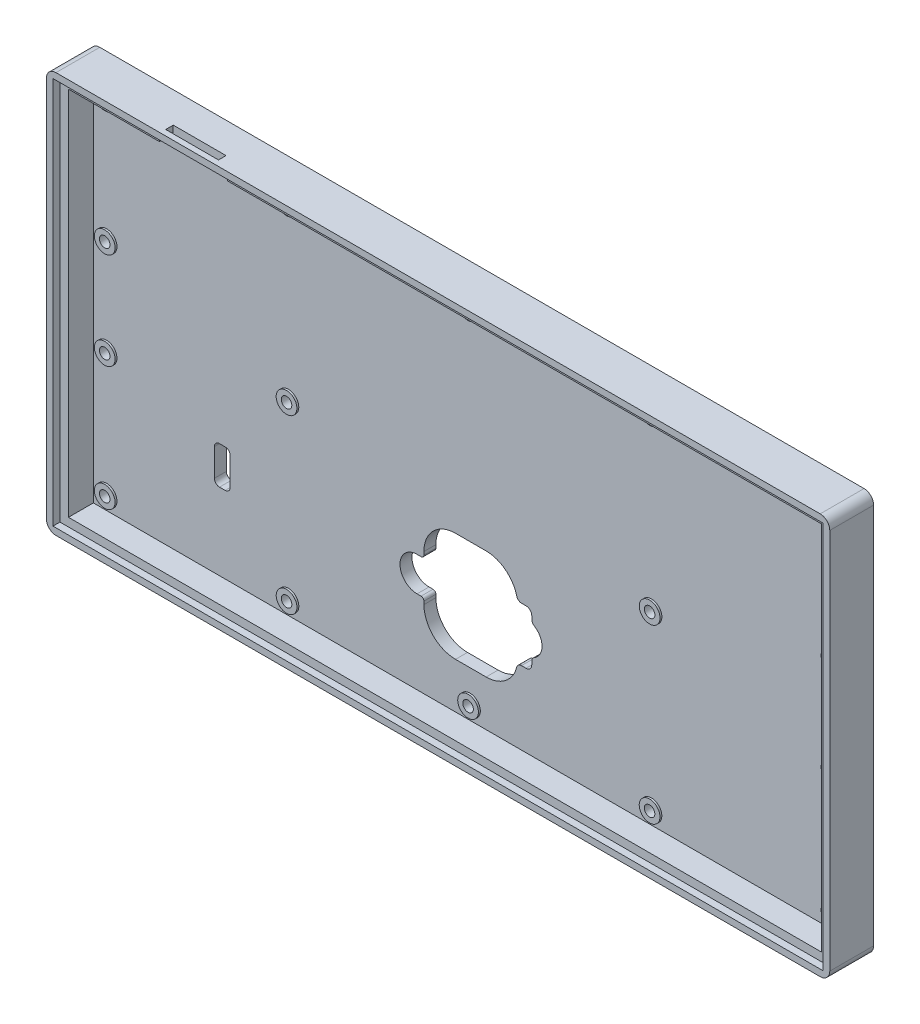
SolidWorks part; units mm, degrees
ref_plane "Front Plane" through (0, 0, 0) normal (0, 0, 1) x (1, 0, 0)
ref_plane "Top Plane" through (0, 0, 0) normal (0, 1, 0) x (1, 0, 0)
ref_plane "Right Plane" through (0, 0, 0) normal (1, 0, 0) x (0, 0, -1)
sketch "PCB" plane through (0, 0, 0) normal (0, 0, 1) x (1, 0, 0)
  line L0 (96.2635, 45.5524) -> (101.8921, 45.5524) construction
  line L1 (-101.8921, 51.181) -> (101.8921, 51.181) construction
  line L2 (-101.8921, 51.181) -> (-101.8921, -51.181) construction
  line L3 (-101.8921, -51.181) -> (101.8921, -51.181) construction
  line L4 (101.8921, 51.181) -> (101.8921, -51.181) construction
  line L5 (-101.8921, 51.181) -> (101.8921, -51.181) construction
  line L6 (-101.8921, -51.181) -> (101.8921, 51.181) construction
  line L7 (96.2635, 45.5524) -> (96.2635, 51.181) construction
  line L8 (-96.2635, 45.5524) -> (-101.8921, 45.5524) construction
  line L9 (-96.2635, -45.5524) -> (-96.2635, -51.181) construction
  line L10 (-92.8243, 0) -> (-92.8243, 25.6794) construction
  line L11 (-98.8568, 31.7119) -> (-86.7918, 31.7119)
  line L12 (-98.8568, 31.7119) -> (-98.8568, 19.6469)
  line L13 (-98.8568, 19.6469) -> (-86.7918, 19.6469)
  line L14 (-86.7918, 31.7119) -> (-86.7918, 19.6469)
  line L15 (-98.8568, 31.7119) -> (-86.7918, 19.6469) construction
  line L16 (-98.8568, 19.6469) -> (-86.7918, 31.7119) construction
  line L17 (-98.8568, 6.0325) -> (-86.7918, 6.0325)
  line L18 (-98.8568, 6.0325) -> (-98.8568, -6.0325)
  line L19 (-98.8568, -6.0325) -> (-86.7918, -6.0325)
  line L20 (-86.7918, 6.0325) -> (-86.7918, -6.0325)
  line L21 (-98.8568, 6.0325) -> (-86.7918, -6.0325) construction
  line L22 (-98.8568, -6.0325) -> (-86.7918, 6.0325) construction
  line L23 (-98.8568, -19.6469) -> (-86.7918, -19.6469)
  line L24 (-98.8568, -19.6469) -> (-98.8568, -31.7119)
  line L25 (-98.8568, -31.7119) -> (-86.7918, -31.7119)
  line L26 (-86.7918, -19.6469) -> (-86.7918, -31.7119)
  line L27 (-98.8568, -19.6469) -> (-86.7918, -31.7119) construction
  line L28 (-98.8568, -31.7119) -> (-86.7918, -19.6469) construction
  line L29 (86.7918, 31.7119) -> (98.8568, 31.7119)
  line L30 (86.7918, 31.7119) -> (86.7918, 19.6469)
  line L31 (86.7918, 19.6469) -> (98.8568, 19.6469)
  line L32 (98.8568, 31.7119) -> (98.8568, 19.6469)
  line L33 (86.7918, 31.7119) -> (98.8568, 19.6469) construction
  line L34 (86.7918, 19.6469) -> (98.8568, 31.7119) construction
  line L35 (86.7918, 6.0325) -> (98.8568, 6.0325)
  line L36 (86.7918, 6.0325) -> (86.7918, -6.0325)
  line L37 (86.7918, -6.0325) -> (98.8568, -6.0325)
  line L38 (98.8568, 6.0325) -> (98.8568, -6.0325)
  line L39 (86.7918, 6.0325) -> (98.8568, -6.0325) construction
  line L40 (86.7918, -6.0325) -> (98.8568, 6.0325) construction
  line L41 (86.7918, -19.6469) -> (98.8568, -19.6469)
  line L42 (86.7918, -19.6469) -> (86.7918, -31.7119)
  line L43 (86.7918, -31.7119) -> (98.8568, -31.7119)
  line L44 (98.8568, -19.6469) -> (98.8568, -31.7119)
  line L45 (86.7918, -19.6469) -> (98.8568, -31.7119) construction
  line L46 (86.7918, -31.7119) -> (98.8568, -19.6469) construction
  line L47 (-92.8243, 0) -> (-92.8243, -25.6794) construction
  line L48 (-92.8243, 25.6794) -> (-101.8921, 25.6794) construction
  line L49 (92.8243, 25.6794) -> (101.8921, 25.6794) construction
  line L50 (-3.114, -17.4711) -> (-3.114, -27.7327) construction
  circle A0 centre (-96.2635, 45.5524) radius 0.9995
  circle A1 centre (-96.2635, -45.5524) radius 0.9995
  circle A2 centre (96.2635, -45.5524) radius 0.9995
  circle A3 centre (96.2635, 45.5524) radius 0.9995
  circle A4 centre (-3.114, -17.4711) radius 1.9939
  circle A5 centre (-3.114, -27.7327) radius 1.9939
  point P0 (0, 0)
  point P14 (-92.8243, 25.6794)
  point P23 (-92.8243, 0)
  point P28 (-92.8243, -25.6794)
  point P33 (92.8243, 25.6794)
  point P38 (92.8243, 0)
  point P43 (92.8243, -25.6794)
  point P54 (0.1092, -22.6019)
  point P55 (-7.5006, -22.6019)
  point P60 (-3.114, -22.6019)
  dimension "D4" = 1.999
  dimension "D14" = 3.9878
  dimension "D1" = 203.7842
  dimension "D2" = 102.362
  dimension "D3" = 5.6286
  dimension "D5" = 25.5016
  dimension "D6" = 25.5016
  dimension "D7" = 9.0678
  dimension "D8" = 12.065
  dimension "D9" = 102.0013
  dimension "D10" = 28.5791
  dimension "D11" = 7.6098
  dimension "D12" = 5.1308
  dimension "D13" = 3.2233
sketch "DT_plug" plane through (0, 0, 0) normal (0, 0, 1) x (1, 0, 0)
  line L0 (29.2774, -40.0231) -> (29.2774, -5.0981) construction
  dimension "D1" = 34.925
sketch "display_screen" plane through (0, 0, 0) normal (0, 0, 1) x (1, 0, 0)
  line L1 (-80.3275, 46.3296) -> (83.7565, 46.3296) construction
  line L2 (-80.3275, 46.3296) -> (-80.3275, -50.9016) construction
  line L3 (-80.3275, -50.9016) -> (83.7565, -50.9016) construction
  line L4 (83.7565, 46.3296) -> (83.7565, -50.9016) construction
  line L5 (-78.2955, 44.2976) -> (78.2955, 44.2976) construction
  line L6 (-78.2955, 44.2976) -> (-78.2955, -44.2976) construction
  line L7 (-78.2955, -44.2976) -> (78.2955, -44.2976) construction
  line L8 (78.2955, 44.2976) -> (78.2955, -44.2976) construction
  point P8 (0, 44.2976)
  point P10 (-78.2955, 0)
  dimension "D1" = 164.084
  dimension "D2" = 97.2312
  dimension "D3" = 6.604
  dimension "D4" = 2.032
  dimension "D5" = 2.032
  dimension "D6" = 5.461
ref_plane "back_of_PCB" through (0, 0, -1.8542) normal (0, 0, 1) x (1, 0, 0)
ref_plane "back_PCB_clearance" through (0, 0, -8.4582) normal (0, 0, 1) x (1, 0, 0)
sketch "Sketch4" plane through (0, 0, 0) normal (0, 0, 1) x (1, 0, 0)
  line L0 (-102.1461, 51.4096) -> (-102.1461, 53.1596) construction
  line L1 (-102.1461, 51.4096) -> (102.1461, 51.4096)
  line L2 (-102.1461, 51.4096) -> (-102.1461, -51.4096)
  line L3 (-102.1461, -51.4096) -> (102.1461, -51.4096)
  line L4 (102.1461, 51.4096) -> (102.1461, -51.4096)
  line L5 (-103.8961, 53.1596) -> (103.8961, 53.1596)
  line L6 (-103.8961, 53.1596) -> (-103.8961, -53.1596)
  line L7 (-103.8961, -53.1596) -> (103.8961, -53.1596)
  line L8 (103.8961, 53.1596) -> (103.8961, -53.1596)
  line L9 (-102.1461, 51.4096) -> (-103.8961, 51.4096) construction
  line L10 (102.1461, -51.4096) -> (102.1461, -53.1596) construction
  line L11 (102.1461, -51.4096) -> (103.8961, -51.4096) construction
  line L12 (-101.8921, 51.181) -> (101.8921, 51.181) construction
  line L13 (-101.8921, 51.181) -> (-101.8921, -51.181) construction
  line L14 (101.8921, 51.181) -> (101.8921, -51.181) construction
  line L15 (-101.8921, -51.181) -> (101.8921, -51.181) construction
  dimension "D1" = 1.75
  dimension "D2" = 0.2286
  dimension "D3" = 0.254
  dimension "D4" = 0.254
  dimension "D5" = 0.2286
extrude "Boss-Extrude1" add sketch "Sketch4" against normal up to surface (1.8542 mm away) up to plane "back_of_PCB"
sketch "Sketch5" plane through (0, 0, -1.8542) normal (0, 0, -1) x (-1, 0, 0)
  line L1 (-103.8961, 53.1596) -> (103.8961, 53.1596)
  line L2 (-103.8961, 53.1596) -> (-103.8961, -53.1596)
  line L3 (-103.8961, -53.1596) -> (103.8961, -53.1596)
  line L4 (103.8961, 53.1596) -> (103.8961, -53.1596)
  line L6 (101.8921, 51.181) -> (-101.8921, 51.181) construction
  line L7 (-99.8931, 49.182) -> (99.8931, 49.182)
  line L8 (-99.8931, 49.182) -> (-99.8931, -49.182)
  line L9 (-99.8931, -49.182) -> (99.8931, -49.182)
  line L10 (99.8931, 49.182) -> (99.8931, -49.182)
  line L11 (-99.8931, 49.182) -> (-99.8931, 51.181) construction
  line L12 (-99.8931, 49.182) -> (-101.8921, 49.182) construction
  line L13 (-101.8921, 51.181) -> (-101.8921, -51.181) construction
  line L14 (99.8931, -49.182) -> (101.8921, -49.182) construction
  line L15 (101.8921, 51.181) -> (101.8921, -51.181) construction
  line L16 (99.8931, -49.182) -> (99.8931, -51.181) construction
  line L17 (101.8921, -51.181) -> (-101.8921, -51.181) construction
  dimension "D1" = 1.999
extrude "Boss-Extrude2" add sketch "Sketch5" along normal up to surface (6.604 mm away) up to plane "back_PCB_clearance"
sketch "Sketch6" plane through (0, 0, -8.4582) normal (0, 0, -1) x (-1, 0, 0)
  line L0 (11.7018, -27.8978) -> (11.7018, -28.6979) construction
  line L1 (-103.8961, 53.1596) -> (103.8961, 53.1596)
  line L2 (-103.8961, 53.1596) -> (-103.8961, -53.1596)
  line L3 (-103.8961, -53.1596) -> (103.8961, -53.1596)
  line L4 (103.8961, 53.1596) -> (103.8961, -53.1596)
  line L5 (3.8278, -8.6319) -> (-4.2865, -8.6319) construction
  line L6 (11.7018, -16.5059) -> (11.7018, -17.306) construction
  line L7 (3.8278, -36.5719) -> (-4.2865, -36.5719) construction
  line L11 (12.9718, -18.576) -> (14.0259, -18.576) construction
  line L13 (12.9718, -26.6278) -> (14.0259, -26.6278) construction
  line L15 (-13.6655, -15.9344) -> (-14.8666, -15.9344) construction
  line L16 (-15.8826, -27.4219) -> (-15.8826, -28.2534) construction
  line L17 (-13.6655, -29.2694) -> (-14.8666, -29.2694) construction
  line L18 (-15.8826, -16.9504) -> (-15.8826, -17.782) construction
  line L20 (12.2098, -27.8978) -> (12.2098, -28.6979)
  line L21 (3.8278, -37.0799) -> (-4.2865, -37.0799)
  line L22 (-13.6655, -29.7774) -> (-14.8666, -29.7774)
  line L23 (-16.3906, -27.4219) -> (-16.3906, -28.2534)
  line L24 (-16.3906, -16.9504) -> (-16.3906, -17.782)
  line L25 (-13.6655, -15.4264) -> (-14.8666, -15.4264)
  line L26 (3.8278, -8.1239) -> (-4.2865, -8.1239)
  line L27 (12.2098, -16.5059) -> (12.2098, -17.306)
  line L28 (12.9718, -18.068) -> (14.0259, -18.068)
  line L29 (12.9718, -27.1358) -> (14.0259, -27.1358)
  arc A0 (-16.7989, -19.407) -> (-16.7989, -25.7969) centre (-14.8666, -22.6019) ccw construction
  arc A1 (12.9718, -18.576) -> (11.7018, -17.306) centre (12.9718, -17.306) cw construction
  arc A2 (12.9718, -26.6278) -> (11.7018, -27.8978) centre (12.9718, -27.8978) ccw construction
  arc A3 (14.0259, -26.6278) -> (14.0259, -18.576) centre (14.0259, -22.6019) ccw construction
  arc A4 (11.7018, -28.6979) -> (3.8278, -36.5719) centre (3.8278, -28.6979) cw construction
  arc A5 (11.7018, -16.5059) -> (3.8278, -8.6319) centre (3.8278, -16.5059) ccw construction
  arc A6 (-4.2865, -8.6319) -> (-11.9202, -14.5755) centre (-4.2865, -16.5059) ccw construction
  arc A7 (-11.9202, -14.5755) -> (-13.6655, -15.9344) centre (-13.6655, -14.1342) cw construction
  arc A8 (-4.2865, -36.5719) -> (-11.9202, -30.6283) centre (-4.2865, -28.6979) cw construction
  arc A9 (-11.9202, -30.6283) -> (-13.6655, -29.2694) centre (-13.6655, -31.0697) ccw construction
  arc A10 (-14.8666, -15.9344) -> (-15.8826, -16.9504) centre (-14.8666, -16.9504) ccw construction
  arc A11 (-15.8826, -17.782) -> (-16.7989, -19.407) centre (-17.7817, -17.782) cw construction
  arc A12 (-15.8826, -27.4219) -> (-16.7989, -25.7969) centre (-17.7817, -27.4219) ccw construction
  arc A13 (-15.8826, -28.2534) -> (-14.8666, -29.2694) centre (-14.8666, -28.2534) ccw construction
  arc A14 (12.2098, -28.6979) -> (3.8278, -37.0799) centre (3.8278, -28.6979) cw
  arc A15 (-4.2865, -37.0799) -> (-12.4127, -30.7529) centre (-4.2865, -28.6979) cw
  arc A16 (-12.4127, -30.7529) -> (-13.6655, -29.7774) centre (-13.6655, -31.0697) ccw
  arc A17 (-16.3906, -28.2534) -> (-14.8666, -29.7774) centre (-14.8666, -28.2534) ccw
  arc A18 (-16.3906, -27.4219) -> (-17.0618, -26.2315) centre (-17.7817, -27.4219) ccw
  arc A19 (-17.0618, -18.9723) -> (-17.0618, -26.2315) centre (-14.8666, -22.6019) ccw
  arc A20 (-16.3906, -17.782) -> (-17.0618, -18.9723) centre (-17.7817, -17.782) cw
  arc A21 (-14.8666, -15.4264) -> (-16.3906, -16.9504) centre (-14.8666, -16.9504) ccw
  arc A22 (-12.4127, -14.451) -> (-13.6655, -15.4264) centre (-13.6655, -14.1342) cw
  arc A23 (-4.2865, -8.1239) -> (-12.4127, -14.451) centre (-4.2865, -16.5059) ccw
  arc A24 (12.2098, -16.5059) -> (3.8278, -8.1239) centre (3.8278, -16.5059) ccw
  arc A25 (12.9718, -18.068) -> (12.2098, -17.306) centre (12.9718, -17.306) cw
  arc A26 (14.0259, -27.1358) -> (14.0259, -18.068) centre (14.0259, -22.6019) ccw
  arc A27 (12.9718, -27.1358) -> (12.2098, -27.8978) centre (12.9718, -27.8978) ccw
  point P6 (-0.1092, -22.6019)
  dimension "D7" = 3.7338
  dimension "D9" = 1.27
  dimension "D3" = 1.0541
  dimension "D10" = 7.874
  dimension "D13" = 1.8002
  dimension "D16" = 1.016
  dimension "D17" = 1.8991
  dimension "D2" = 11.811
  dimension "D4" = 13.97
  dimension "D5" = 15.7734
  dimension "D6" = 6.6675
  dimension "D8" = 1.016
  dimension "D11" = 0.8001
  dimension "D12" = 13.97
  dimension "D14" = 8.1143
  dimension "D15" = 6.6675
  dimension "D22" = 0.508
extrude "Boss-Extrude3" add sketch "Sketch6" along normal blind 3.175
sketch "mounting_bolt_pattern" plane through (0, 0, -11.6332) normal (0, 0, -1) x (-1, 0, 0)
  line L0 (-38.1, 22.225) -> (38.1, 22.225) construction
  line L1 (38.1, 22.225) -> (38.1, -22.225) construction
  line L3 (38.1, 22.225) -> (38.1, 53.1596) construction
  line L4 (-103.8961, 53.1596) -> (103.8961, 53.1596) construction
  line L5 (38.1, -22.225) -> (38.1, -53.1596) construction
  line L6 (103.8961, -53.1596) -> (-103.8961, -53.1596) construction
  circle A0 centre (-38.1, 22.225) radius 2.032
  circle A1 centre (-38.1, 22.225) radius 5.207 construction
  circle A2 centre (-38.1, -22.225) radius 5.207 construction
  circle A3 centre (-38.1, -22.225) radius 2.032
  circle A4 centre (38.1, -22.225) radius 2.032
  circle A5 centre (38.1, -22.225) radius 5.207 construction
  circle A6 centre (38.1, 22.225) radius 2.032
  circle A7 centre (38.1, 22.225) radius 5.207 construction
  point P12 (0, 22.225)
  dimension "D1" = 4.064
  dimension "D2" = 3.175
  dimension "D3" = 76.2
  dimension "D4" = 44.45
fillet "Fillet1" radius 2.54 4 edges at (103.8961, 53.1596, -5.8166) (103.8961, -53.1596, -5.8166) (-103.8961, -53.1596, -5.8166) (-103.8961, 53.1596, -5.8166)
sketch "Sketch11" plane through (0, 0, -8.4582) normal (0, 0, 1) x (1, 0, 0)
  line L0 (-96.3835, 45.671) -> (-96.3835, 51.4096) construction
  line L1 (-96.3835, 45.671) -> (96.3835, 45.671) construction
  line L2 (-96.3835, 45.671) -> (-96.3835, -45.671) construction
  line L3 (-96.3835, -45.671) -> (96.3835, -45.671) construction
  line L4 (96.3835, 45.671) -> (96.3835, -45.671) construction
  line L5 (-102.1461, 51.4096) -> (102.1461, 51.4096) construction
  line L6 (-96.3835, 45.671) -> (-102.1461, 45.671) construction
  line L7 (-102.1461, 51.4096) -> (-102.1461, -51.4096) construction
  line L8 (96.3835, -45.671) -> (102.1461, -45.671) construction
  line L9 (102.1461, -51.4096) -> (102.1461, 51.4096) construction
  line L10 (96.3835, -45.671) -> (96.3835, -51.4096) construction
  line L11 (102.1461, -51.4096) -> (-102.1461, -51.4096) construction
  circle A0 centre (-96.3835, 45.671) radius 1.4
  circle A1 centre (0, 45.671) radius 1.4
  circle A2 centre (96.3835, 45.671) radius 1.4
  circle A3 centre (-96.3835, -45.671) radius 1.4
  circle A4 centre (96.3835, -45.671) radius 1.4
  circle A5 centre (96.3835, -12.808) radius 1.4
  circle A6 centre (96.3835, 12.808) radius 1.4
  circle A7 centre (0, -45.671) radius 1.4
  circle A8 centre (-96.3835, -12.808) radius 1.4
  circle A9 centre (-96.3835, 12.808) radius 1.4
  circle A10 centre (-48.1435, 45.671) radius 1.4
  circle A11 centre (48.1435, 45.671) radius 1.4
  circle A12 centre (48.1435, -45.671) radius 1.4
  circle A13 centre (-48.1435, -45.671) radius 1.4
  circle A14 centre (-48.1545, 0.033) radius 1.4
  circle A15 centre (48.1545, 0.033) radius 1.4
  dimension "D3" = 2.8
  dimension "D1" = 91.342
  dimension "D2" = 192.767
  dimension "D4" = 48.24
  dimension "D5" = 48.24
  dimension "D6" = 32.863
  dimension "D7" = 32.863
  dimension "D8" = 48.229
  dimension "D9" = 45.638
  dimension "D10" = 48.229
  dimension "D11" = 45.638
extrude "Cut-Extrude2" cut sketch "Sketch11" against normal up to next
sketch "Sketch12" plane through (0, 53.1596, 0) normal (0, 1, 0) x (1, 0, 0)
  line L0 (101.3561, 0) -> (-101.3561, 0) construction
  line L1 (-73.7461, 3.5) -> (-59.7461, 3.5)
  line L2 (-73.7461, 3.5) -> (-73.7461, 1.5)
  line L3 (-73.7461, 1.5) -> (-59.7461, 1.5)
  line L4 (-59.7461, 3.5) -> (-59.7461, 1.5)
  line L6 (-103.8961, 0) -> (-103.8961, 11.6332) construction
  dimension "D1" = 1.5
  dimension "D2" = 14
  dimension "D3" = 30.15
  dimension "D4" = 2
extrude "Cut-Extrude3" cut sketch "Sketch12" against normal up to next
sketch "Sketch13" plane through (0, 0, -1.8542) normal (0, 0, 1) x (1, 0, 0)
  line L0 (-59.7461, 51.4096) -> (102.1461, 51.4096) construction
  line L1 (-75.7461, 49.182) -> (-57.7461, 49.182)
  line L2 (-75.7461, 49.182) -> (-75.7461, 51.4096)
  line L3 (-75.7461, 51.4096) -> (-57.7461, 51.4096)
  line L4 (-57.7461, 49.182) -> (-57.7461, 51.4096)
  line L5 (99.8931, 49.182) -> (-99.8931, 49.182) construction
  line L6 (-73.7461, 51.4096) -> (-73.7461, 49.182) construction
  line L7 (-59.7461, 49.182) -> (-59.7461, 53.1596) construction
  dimension "D1" = 2
  dimension "D2" = 2
extrude "Cut-Extrude4" cut sketch "Sketch13" against normal up to surface (1.6458 mm away) up to face at (-66.7461, 51.1708, -3.5)
sketch "Sketch14" plane through (0, 0, -8.4582) normal (0, 0, 1) x (1, 0, 0)
  circle A0 centre (-96.3835, 45.671) radius 1.4
  circle A1 centre (-96.3835, 45.671) radius 2.75
  circle A3 centre (-96.3835, 45.671) radius 1.4 construction
  circle A4 centre (-48.1435, 45.671) radius 2.75
  circle A5 centre (-48.1435, 45.671) radius 1.4
  circle A6 centre (0, 45.671) radius 1.4
  circle A7 centre (0, 45.671) radius 2.75
  circle A8 centre (48.1435, 45.671) radius 1.4
  circle A9 centre (48.1435, 45.671) radius 2.75
  circle A10 centre (96.3835, 45.671) radius 1.4
  circle A11 centre (96.3835, 45.671) radius 2.75
  circle A12 centre (-96.3835, 12.808) radius 1.4
  circle A13 centre (-96.3835, 12.808) radius 2.75
  circle A14 centre (-48.1545, 0.033) radius 1.4
  circle A15 centre (-48.1545, 0.033) radius 2.75
  circle A16 centre (-96.3835, -12.808) radius 1.4
  circle A17 centre (-96.3835, -12.808) radius 2.75
  circle A18 centre (-96.3835, -45.671) radius 1.4
  circle A19 centre (-96.3835, -45.671) radius 2.75
  circle A20 centre (-48.1435, -45.671) radius 1.4
  circle A21 centre (-48.1435, -45.671) radius 2.75
  circle A22 centre (0, -45.671) radius 1.4
  circle A23 centre (0, -45.671) radius 2.75
  circle A24 centre (48.1545, 0.033) radius 1.4
  circle A25 centre (48.1545, 0.033) radius 2.75
  circle A26 centre (48.1435, -45.671) radius 1.4
  circle A27 centre (48.1435, -45.671) radius 2.75
  circle A28 centre (96.3835, -45.671) radius 1.4
  circle A29 centre (96.3835, -45.671) radius 2.75
  circle A30 centre (96.3835, -12.808) radius 1.4
  circle A31 centre (96.3835, -12.808) radius 2.75
  circle A32 centre (96.3835, 12.808) radius 1.4
  circle A33 centre (96.3835, 12.808) radius 2.75
  circle A34 centre (-48.1435, 45.671) radius 1.4 construction
  circle A35 centre (0, 45.671) radius 1.4 construction
  circle A36 centre (48.1435, 45.671) radius 1.4 construction
  circle A37 centre (96.3835, 45.671) radius 1.4 construction
  circle A38 centre (96.3835, 12.808) radius 1.4 construction
  circle A39 centre (48.1545, 0.033) radius 1.4 construction
  circle A40 centre (-48.1545, 0.033) radius 1.4 construction
  circle A41 centre (-96.3835, 12.808) radius 1.4 construction
  circle A42 centre (-96.3835, -12.808) radius 1.4 construction
  circle A43 centre (-96.3835, -45.671) radius 1.4 construction
  circle A44 centre (-48.1435, -45.671) radius 1.4 construction
  circle A45 centre (0, -45.671) radius 1.4 construction
  circle A46 centre (48.1435, -45.671) radius 1.4 construction
  circle A47 centre (96.3835, -45.671) radius 1.4 construction
  circle A48 centre (96.3835, -12.808) radius 1.4 construction
  dimension "D1" = 5.5
extrude "Boss-Extrude4" add sketch "Sketch14" along normal blind 0.5
sketch "Sketch15" plane through (0, 0, -8.4582) normal (0, 0, 1) x (1, 0, 0)
  line L0 (-99.8931, 49.182) -> (-99.8931, -49.182) construction
  line L1 (-66.4371, -18.827) -> (-64.9371, -18.827)
  line L2 (-67.7871, -20.177) -> (-67.7871, -27.477)
  line L3 (-66.4371, -28.827) -> (-64.9371, -28.827)
  line L4 (-63.5871, -20.177) -> (-63.5871, -27.477)
  line L5 (-99.8931, -49.182) -> (99.8931, -49.182) construction
  arc A0 (-64.9371, -28.827) -> (-63.5871, -27.477) centre (-64.9371, -27.477) ccw
  arc A1 (-67.7871, -27.477) -> (-66.4371, -28.827) centre (-66.4371, -27.477) ccw
  arc A2 (-66.4371, -18.827) -> (-67.7871, -20.177) centre (-66.4371, -20.177) ccw
  arc A3 (-64.9371, -18.827) -> (-63.5871, -20.177) centre (-64.9371, -20.177) cw
  point P10 (-63.5871, -28.827)
  point P13 (-67.7871, -28.827)
  point P16 (-67.7871, -18.827)
  dimension "D5" = 1.35
  dimension "D1" = 32.106
  dimension "D2" = 4.2
  dimension "D3" = 10
  dimension "D4" = 20.355
extrude "Cut-Extrude5" cut sketch "Sketch15" against normal up to next
